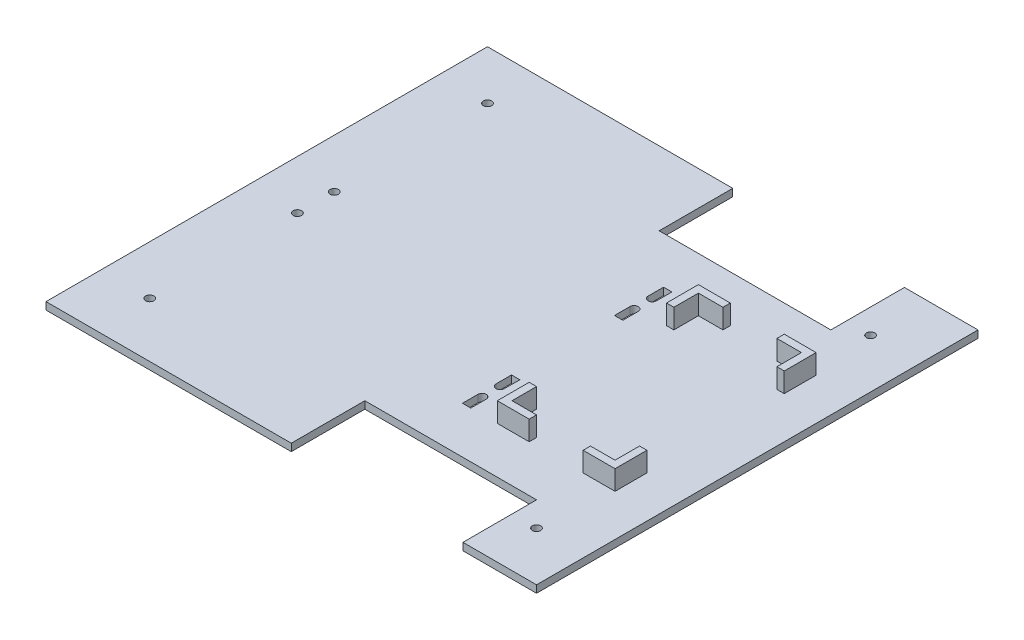
SolidWorks part; units mm, degrees
ref_plane "Front Plane" through (0, 0, 0) normal (0, 0, 1) x (1, 0, 0)
ref_plane "Top Plane" through (0, 0, 0) normal (0, 1, 0) x (1, 0, 0)
ref_plane "Right Plane" through (0, 0, 0) normal (1, 0, 0) x (0, 0, -1)
sketch "Sketch1" plane through (0, 0, 0) normal (0, 1, 0) x (1, 0, 0)
  line L0 (-48.9431, 29.6359) -> (1729.0569, 29.6359)
  line L1 (1729.0569, 29.6359) -> (1729.0569, -732.3641)
  line L2 (-48.9431, 29.6359) -> (-48.9431, -732.3641)
  line L3 (1729.0569, -732.3641) -> (2491.0569, -732.3641)
  line L4 (2491.0569, -732.3641) -> (2491.0569, 3839.6359)
  line L5 (2491.0569, 3839.6359) -> (1729.0569, 3839.6359)
  line L6 (1729.0569, 3839.6359) -> (1729.0569, 3077.6359)
  line L7 (1729.0569, 3077.6359) -> (-48.9431, 3077.6359)
  line L8 (-48.9431, 3077.6359) -> (-48.9431, 3839.6359)
  line L9 (-48.9431, 3839.6359) -> (-2588.9431, 3839.6359)
  line L10 (-2588.9431, 3839.6359) -> (-2588.9431, -732.3641)
  line L11 (-2588.9431, -732.3641) -> (-48.9431, -732.3641)
  line L19 (565.7369, 2435.0159) -> (565.7369, 2595.0359)
  line L20 (565.7369, 2595.0359) -> (479.3769, 2595.0359)
  line L21 (479.3769, 2595.0359) -> (479.3769, 2435.0159)
  line L23 (565.7369, 2247.0559) -> (565.7369, 2087.0359)
  line L24 (565.7369, 2087.0359) -> (479.3769, 2087.0359)
  line L25 (479.3769, 2087.0359) -> (479.3769, 2247.0559)
  line L26 (479.3769, 1020.2359) -> (479.3769, 860.2159)
  line L27 (565.7369, 1020.2359) -> (479.3769, 1020.2359)
  line L28 (565.7369, 860.2159) -> (565.7369, 1020.2359)
  line L30 (479.3769, 512.2359) -> (479.3769, 672.2559)
  line L31 (565.7369, 512.2359) -> (479.3769, 512.2359)
  line L32 (565.7369, 672.2559) -> (565.7369, 512.2359)
  circle A0 centre (-2080.9431, -166.5082) radius 43.18
  circle A1 centre (-2080.9431, 1744.1359) radius 43.18
  circle A2 centre (-2080.9431, 1363.1359) radius 43.18
  arc A3 (479.3769, 2435.0159) -> (565.7369, 2435.0159) centre (522.5569, 2435.0159) ccw
  arc A4 (565.7369, 2247.0559) -> (479.3769, 2247.0559) centre (522.5569, 2247.0559) ccw
  arc A5 (565.7369, 860.2159) -> (479.3769, 860.2159) centre (522.5569, 860.2159) cw
  arc A6 (479.3769, 672.2559) -> (565.7369, 672.2559) centre (522.5569, 672.2559) cw
  circle A7 centre (-2080.9431, 3331.6359) radius 43.18
  circle A8 centre (1983.0569, -224.3641) radius 43.18
  circle A9 centre (1983.0569, 3235.0991) radius 43.18
extrude "Boss-Extrude1" add sketch "Sketch1" along normal blind 76.2
sketch "Sketch2" plane through (0, 76.2, 0) normal (0, 1, 0) x (1, 0, 0)
  line L0 (2059.2569, 512.2359) -> (2059.2569, 842.4359)
  line L2 (1983.0569, 842.4359) -> (1983.0569, 588.4359)
  line L3 (1983.0569, 588.4359) -> (1729.0569, 588.4359)
  line L4 (840.0569, 842.4359) -> (916.2569, 842.4359)
  line L5 (1170.2569, 512.2359) -> (1170.2569, 588.4359)
  line L6 (840.0569, 512.2359) -> (1170.2569, 512.2359)
  line L8 (840.0569, 2595.0359) -> (840.0569, 2264.8359)
  line L9 (2059.2569, 512.2359) -> (1729.0569, 512.2359)
  line L10 (1729.0569, 512.2359) -> (1729.0569, 588.4359)
  line L11 (2059.2569, 842.4359) -> (1983.0569, 842.4359)
  line L12 (916.2569, 588.4359) -> (1170.2569, 588.4359)
  line L13 (916.2569, 842.4359) -> (916.2569, 588.4359)
  line L14 (840.0569, 512.2359) -> (840.0569, 842.4359)
  line L15 (916.2569, 2264.8359) -> (916.2569, 2518.8359)
  line L16 (916.2569, 2518.8359) -> (1170.2569, 2518.8359)
  line L17 (2059.2569, 2264.8359) -> (1983.0569, 2264.8359)
  line L18 (1729.0569, 2595.0359) -> (1729.0569, 2518.8359)
  line L19 (2059.2569, 2595.0359) -> (1729.0569, 2595.0359)
  line L20 (840.0569, 2595.0359) -> (1170.2569, 2595.0359)
  line L21 (1170.2569, 2595.0359) -> (1170.2569, 2518.8359)
  line L22 (840.0569, 2264.8359) -> (916.2569, 2264.8359)
  line L23 (1983.0569, 2518.8359) -> (1729.0569, 2518.8359)
  line L24 (1983.0569, 2264.8359) -> (1983.0569, 2518.8359)
  line L25 (2059.2569, 2595.0359) -> (2059.2569, 2264.8359)
  point P1 (0, 0)
extrude "Boss-Extrude4" add sketch "Sketch2" along normal blind 203.2
